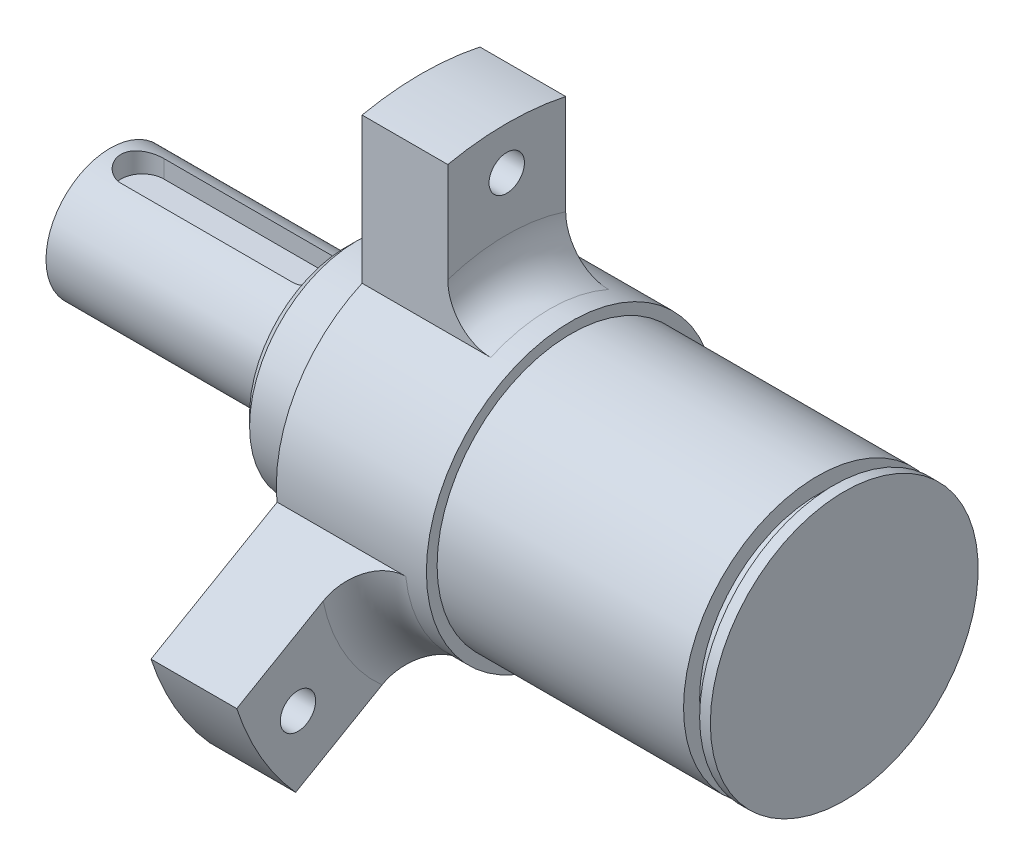
SolidWorks part; units mm, degrees
material "1060 合金"
ref_plane "前视基准面" through (0, 0, 0) normal (0, 0, 1) x (1, 0, 0)
ref_plane "上视基准面" through (0, 0, 0) normal (0, 1, 0) x (1, 0, 0)
ref_plane "右视基准面" through (0, 0, 0) normal (1, 0, 0) x (0, 0, -1)
sketch "草图2" plane through (0, 0, 0) normal (0, 0, 1) x (1, 0, 0)
  line L0 (0, 0) -> (170.3744, 0) construction
  line L2 (0, 0) -> (10, 0)
  line L3 (0, 10) -> (0, 26.5)
  line L4 (0, 26.5) -> (8, 26.5)
  line L5 (8, 13.5) -> (8, 26.5)
  line L6 (10, 0) -> (39.5, 0)
  line L7 (0, 0) -> (-7, 0)
  line L8 (14, 12.5) -> (39.5, 12.5)
  line L9 (39.5, 0) -> (39.5, 12.5)
  line L11 (8, 13.5) -> (14, 13.5)
  line L12 (14, 12.5) -> (14, 13.5)
  line L13 (0, 10) -> (-7, 10)
  line L14 (-7, 0) -> (-7, 10)
  dimension "D1" = 26.5
  dimension "D2" = 8
  dimension "D3" = 6
  dimension "D4" = 12.5
  dimension "D5" = 1
  dimension "D6" = 25.5
  dimension "D7" = 10
  dimension "D8" = 7
revolve "旋转1" add sketch "草图2" angle 360 about L0
sketch "草图3" plane through (39.5, 0, 0) normal (1, 0, 0) x (0, 0, -1)
  line L0 (0, 0) -> (0, 22.0591) construction
  line L3 (-2, 5.6569) -> (-2, 8)
  line L4 (-2, 8) -> (2, 8)
  line L5 (2, 5.6569) -> (2, 8)
  line L6 (-2.2567, 3.7433) -> (2, 8) construction
  line L7 (-2, 8) -> (2.2567, 3.7433) construction
  arc A0 (-2, 5.6569) -> (2, 5.6569) centre (0, 0) ccw
  point P3 (0, 6)
  dimension "D1" = 12
  dimension "D2" = 4
  dimension "D3" = 8
extrude "键槽轴孔" [suppressed] cut sketch "草图3" against normal through all
sketch "草图8" plane through (0, 0, 0) normal (0, 1, 0) x (1, 0, 0)
  line L0 (0, 0) -> (67.4134, 0) construction
  line L1 (39.5, 12.5) -> (14, 12.5) construction
  line L2 (37, 12.5) -> (38.5, 12.5)
  line L3 (37, 12.5) -> (37, 11)
  line L4 (37, 11) -> (38.5, 11)
  line L5 (38.5, 12.5) -> (38.5, 11)
  line L6 (39.5, -12.5) -> (39.5, 12.5) construction
  dimension "D1" = 1
  dimension "D2" = 1.5
  dimension "D3" = 1.5
revolve "卡簧槽" cut sketch "草图8" angle 360 about L0
hole_wizard "M4 螺纹孔1" positions "草图5" profile "草图4" tap size "M4" standard "GB"
sketch "草图5" plane through (0, 0, 0) normal (-1, 0, 0) x (0, 0, 1)
  line L0 (0, 0) -> (0, 25.1605) construction
  circle A0 centre (0, 0) radius 22.5
  circle A1 centre (0, 0) radius 26.5 construction
  point P0 (0, 22.5)
  point P36 (19.4856, -11.25)
  point P37 (-19.4856, -11.25)
  dimension "D1" = 45
  dimension "D2" = 3
sketch "草图4" plane through (0, 22.5, 0) normal (0, 1, 0) x (0, 0, 1)
  line L0 (0, 0) -> (0, 11.0914)
  line L1 (0, 11.0914) -> (1.65, 10.1)
  line L2 (1.65, 10.1) -> (1.65, 0)
  line L5 (1.65, 0) -> (0, 0)
  line L10 (0, 11.0914) -> (-1.65, 10.1) construction
  line L11 (0, -6.35) -> (0, 107.95) construction
  dimension "螺纹孔钻头直径" = 3.3
  dimension "螺纹孔钻头深度" = 10.1
  dimension "导头角度" = 118
cosmetic thread "孔螺蚊线1" parameters "D1"=8, "D2"=4
cosmetic thread "孔螺蚊线2" parameters "D1"=8, "D2"=4
cosmetic thread "孔螺蚊线3" parameters "D1"=8, "D2"=4
fillet "圆角1" radius 4 1 edges at (8, 0, 13.5)
sketch "草图13" plane through (0, 0, 0) normal (-1, 0, 0) x (0, 0, 1)
  line L0 (0, 31.1882) -> (0, 0) construction
  line L1 (-5.5, 12.3288) -> (-5.5, 25.923)
  line L2 (5.5, 12.3288) -> (5.5, 25.923)
  line L3 (13.4271, -1.4013) -> (25.1999, -8.1983)
  line L4 (7.9271, -10.9276) -> (19.6999, -17.7246)
  line L5 (-7.9271, -10.9276) -> (-19.6999, -17.7246)
  line L6 (-13.4271, -1.4013) -> (-25.1999, -8.1983)
  circle A1 centre (0, 0) radius 26.5 construction
  circle A3 centre (0, 0) radius 13.5 construction
  arc A4 (-5.5, 25.923) -> (-25.1999, -8.1983) centre (0, 0) ccw
  arc A5 (-5.5, 12.3288) -> (-13.4271, -1.4013) centre (0, 0) ccw
  arc A6 (13.4271, -1.4013) -> (5.5, 12.3288) centre (0, 0) ccw
  arc A7 (25.1999, -8.1983) -> (5.5, 25.923) centre (0, 0) ccw
  arc A8 (-19.6999, -17.7246) -> (19.6999, -17.7246) centre (0, 0) ccw
  arc A9 (-7.9271, -10.9276) -> (7.9271, -10.9276) centre (0, 0) ccw
  dimension "D1" = 11
extrude "切除-拉伸2" cut sketch "草图13" against normal up to next
chamfer "倒角1" distance 1 angle 45 1 edges at (-7, 0, 10)
sketch "草图14" plane through (-7, 0, 0) normal (-1, 0, 0) x (0, 0, 1)
  circle A0 centre (0, 0) radius 6
  dimension "D1" = 12
extrude "凸台-拉伸1" add sketch "草图14" along normal blind 22
chamfer "倒角2" distance 1 angle 45 1 edges at (-7, 0, -6)
sketch "草图17" plane through (0, 0, 0) normal (0, 1, 0) x (1, 0, 0)
  line L0 (-26, 0) -> (-10, 0) construction
  line L1 (-26, 2) -> (-10, 2)
  line L2 (-26, -2) -> (-10, -2)
  line L3 (-29, 6) -> (-29, -6) construction
  arc A0 (-26, 2) -> (-26, -2) centre (-26, 0) ccw
  arc A1 (-10, -2) -> (-10, 2) centre (-10, 0) ccw
  point P3 (-18, 0)
  dimension "D3" = 1
  dimension "D1" = 16
  dimension "D2" = 4
extrude "切除-拉伸3" cut sketch "草图17" against normal blind 2 from offset 6
